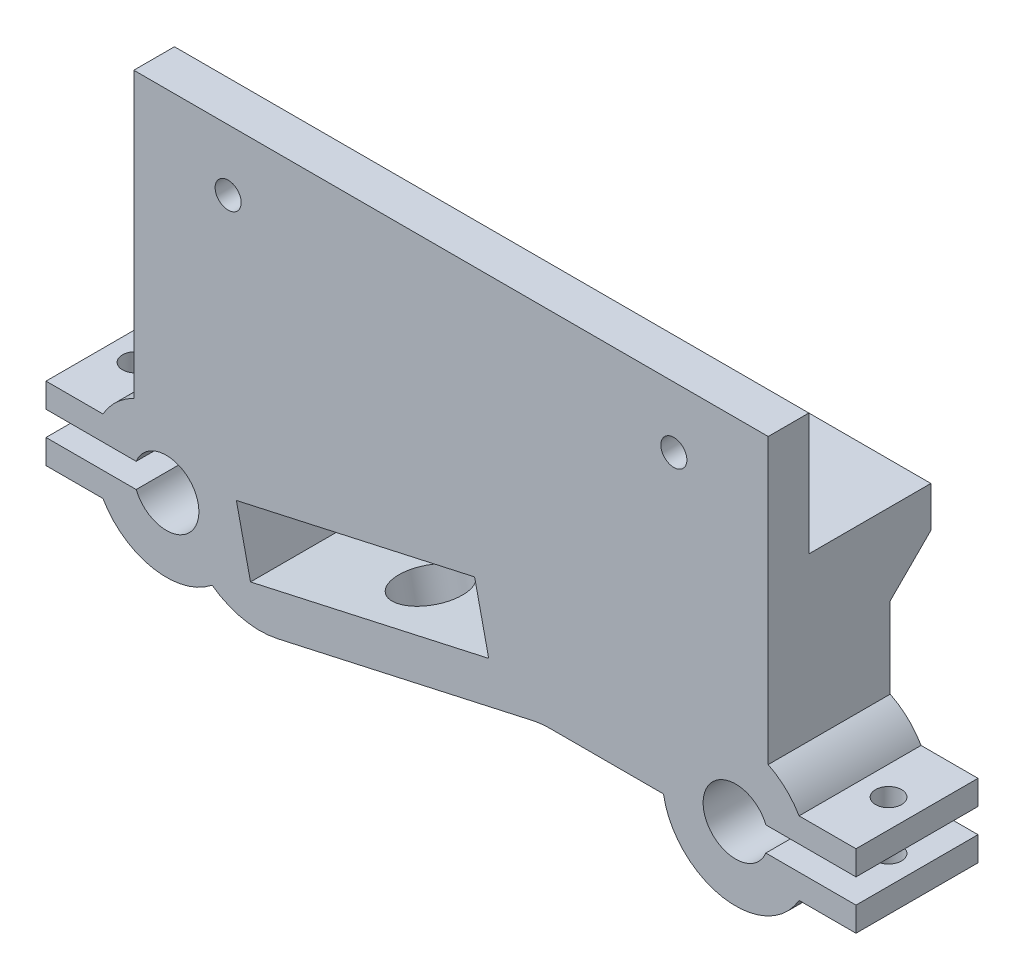
SolidWorks part; units mm, degrees
ref_plane "Front Plane" through (0, 0, 0) normal (0, 0, 1) x (1, 0, 0)
ref_plane "Top Plane" through (0, 0, 0) normal (0, 1, 0) x (1, 0, 0)
ref_plane "Right Plane" through (0, 0, 0) normal (1, 0, 0) x (0, 0, -1)
sketch "Sketch1" plane through (0, 0, 0) normal (0, 0, 1) x (1, 0, 0)
  line L0 (0, -1000) -> (0, 49000) construction
  line L1 (-39, 28) -> (39, 28)
  line L2 (39, 28) -> (39, 8.0623)
  line L3 (36.951, -8.786) -> (-23.8235, -22.2816)
  line L4 (-39, 28) -> (-39, 8.0623)
  line L6 (-34, 23) -> (34, 23)
  line L7 (34, 23) -> (34, 8.9443)
  line L9 (-13.0714, 45.025) -> (10825.8602, -48765.5982) construction
  line L10 (-1035, 0) -> (48965, 0) construction
  line L11 (-34, 23) -> (-34, 8.9443)
  line L12 (-22.3817, -16.8397) -> (-31.7139, -8.3786)
  line L13 (-23.8235, -22.2816) -> (-41.0451, -6.6675)
  line L14 (27.9966, -5.6526) -> (-22.3817, -16.8397)
  line L15 (-49.7942, 4.5) -> (-42.7942, 4.5)
  line L16 (-49.7942, 4.5) -> (-49.7942, 1.5)
  line L17 (-49.7942, 1.5) -> (-38.7081, 1.5)
  line L18 (42.7942, 4.5) -> (49.7942, 4.5)
  line L19 (-49.7942, -1.5) -> (-38.7081, -1.5)
  line L20 (-49.7942, -1.5) -> (-49.7942, -4.5)
  line L21 (-49.7942, -4.5) -> (-42.7942, -4.5)
  line L23 (38.7081, 1.5) -> (49.7942, 1.5)
  line L24 (49.7942, 4.5) -> (49.7942, 1.5)
  line L25 (38.7081, -1.5) -> (49.7942, -1.5)
  line L27 (42.7942, -4.5) -> (49.7942, -4.5)
  line L28 (49.7942, -1.5) -> (49.7942, -4.5)
  arc A0 (-38.7081, -1.5) -> (-38.7081, 1.5) centre (-35, 0) ccw
  arc A1 (38.7081, 1.5) -> (38.7081, -1.5) centre (35, 0) ccw
  arc A2 (34, 8.9443) -> (27.9966, -5.6526) centre (35, 0) ccw
  arc A3 (-39, 8.0623) -> (-42.7942, 4.5) centre (-35, 0) ccw
  arc A4 (-42.7942, -4.5) -> (-41.0451, -6.6675) centre (-35, 0) ccw
  arc A5 (-31.7139, -8.3786) -> (-34, 8.9443) centre (-35, 0) ccw
  arc A6 (36.951, -8.786) -> (42.7942, -4.5) centre (35, 0) ccw
  arc A8 (42.7942, 4.5) -> (39, 8.0623) centre (35, 0) ccw
  dimension "D1" = 8
  dimension "D2" = 70
  dimension "D4" = 18
  dimension "D5" = 19
  dimension "D14" = 9
  dimension "D3" = 102.52
  dimension "D6" = 5
  dimension "D7" = 5
  dimension "D8" = 3
  dimension "D9" = 3
  dimension "D10" = 22.5
  dimension "D11" = 5
  dimension "D12" = 5
  dimension "D13" = 3
  dimension "D15" = 7
  dimension "D16" = 3
  dimension "D17" = 7
  dimension "D18" = 5
  dimension "D19" = 90
  dimension "D20" = 3
sketch "Sketch2" plane through (0, 0, 0) normal (0, 0, 1) x (1, 0, 0)
  line L0 (-39, 28) -> (39, 28)
  line L1 (39, 28) -> (39, 8.0623)
  line L2 (-39, 28) -> (-39, 8.0623)
  line L3 (-42.7942, 4.5) -> (-49.7942, 4.5)
  line L4 (-49.7942, 4.5) -> (-49.7942, 1.5)
  line L5 (-49.7942, 1.5) -> (-38.7081, 1.5)
  line L6 (-38.7081, -1.5) -> (-49.7942, -1.5)
  line L7 (-49.7942, -1.5) -> (-49.7942, -4.5)
  line L8 (-49.7942, -4.5) -> (-42.7942, -4.5)
  line L9 (11.0821, -1.5) -> (-25.8131, -9.693)
  line L10 (42.7942, 4.5) -> (49.7942, 4.5)
  line L11 (49.7942, 4.5) -> (49.7942, 1.5)
  line L12 (49.7942, 1.5) -> (38.7081, 1.5)
  line L13 (38.7081, -1.5) -> (49.7942, -1.5)
  line L14 (49.7942, -1.5) -> (49.7942, -4.5)
  line L15 (49.7942, -4.5) -> (42.7942, -4.5)
  line L16 (-25.8131, -9.693) -> (-29.3708, -7.0223)
  line L17 (26.1259, -1.5) -> (11.0821, -1.5)
  line L19 (27.9966, -5.6526) -> (-22.3817, -16.8397) construction
  line L20 (-43369.1498, 195289.1042) -> (54181.9386, -244009.6774) construction
  line L21 (-23.3484, 3.6588) -> (0.0809, 8.8615) construction
  line L22 (-23.3484, 3.6588) -> (-21.8309, -3.1747) construction
  line L23 (-21.8309, -3.1747) -> (1.5984, 2.028) construction
  line L24 (0.0809, 8.8615) -> (1.5984, 2.028) construction
  line L25 (-16.9288, 30.1055) -> (10822.0908, -48780.9143) construction
  line L27 (-24.6512, -4.3132) -> (-26.3854, 3.4966)
  line L28 (-26.3854, 3.4966) -> (2.9012, 10)
  line L29 (2.9012, 10) -> (4.6354, 2.1902)
  line L30 (4.6354, 2.1902) -> (-24.6512, -4.3132)
  line L32 (2.9012, 10) -> (-1.0959, 28) construction
  arc A0 (-39, 8.0623) -> (-42.7942, 4.5) centre (-35, 0) ccw
  arc A1 (-39, 8.0623) -> (-42.7942, 4.5) centre (-35, 0) ccw construction
  arc A2 (39, 8.0623) -> (42.7942, 4.5) centre (35, 0) cw
  arc A3 (42.7942, 4.5) -> (39, 8.0623) centre (35, 0) ccw construction
  arc A4 (42.7942, -4.5) -> (26.1259, -1.5) centre (35, 0) cw
  arc A5 (-42.7942, -4.5) -> (-29.3708, -7.0223) centre (-35, 0) ccw
  arc A6 (-38.7081, 1.5) -> (-38.7081, -1.5) centre (-35, 0) cw
  arc A7 (-38.7081, -1.5) -> (-38.7081, 1.5) centre (-35, 0) ccw construction
  arc A8 (38.7081, 1.5) -> (38.7081, -1.5) centre (35, 0) ccw
  arc A9 (38.7081, 1.5) -> (38.7081, -1.5) centre (35, 0) ccw construction
  dimension "D1" = 24
  dimension "D2" = 5
  dimension "D3" = 7
  dimension "D4" = 30
  dimension "D5" = 8
  dimension "D6" = 0.5
  dimension "D7" = 18
  dimension "D8" = 5
  dimension "D9" = 5
extrude "Boss-Extrude1" add sketch "Sketch2" against normal blind 15
sketch "Sketch3" plane through (0, 0, -15) normal (0, 0, -1) x (-1, 0, 0)
  line L0 (-34, 8.9443) -> (-34, 23)
  line L1 (-34, 23) -> (34, 23)
  line L2 (34, 23) -> (34, 8.9443)
  line L3 (-30.9373, 8.0309) -> (24.6512, -4.3132)
  line L4 (24.6512, -4.3132) -> (-4.6354, 2.1902) construction
  line L5 (24.6512, -4.3132) -> (26.3854, 3.4966)
  line L6 (26.3854, 3.4966) -> (27.0373, 4.1946)
  arc A0 (-27.9966, -5.6526) -> (-34, 8.9443) centre (-35, 0) ccw construction
  arc A2 (34, 8.9443) -> (27.0373, 4.1946) centre (35, 0) ccw
  arc A3 (-34, 8.9443) -> (-30.9373, 8.0309) centre (-35, 0) cw
extrude "Cut-Extrude1" cut sketch "Sketch3" against normal blind 13
sketch "Sketch4" plane through (0, 0, -2) normal (0, 0, -1) x (-1, 0, 0)
  line L0 (5.8848, 8.049) -> (7.619, 15.8587)
  line L1 (26.3854, 3.4966) -> (-2.9012, 10) construction
  line L2 (19.3337, 13.2574) -> (17.5994, 5.4476)
  line L3 (7.619, 15.8587) -> (19.3337, 13.2574)
  line L4 (5.8848, 8.049) -> (17.5994, 5.4476)
  line L5 (9.8325, -1.8514) -> (10848.8521, 48809.1684) construction
  line L6 (43369.1498, 195289.1042) -> (-54181.9386, -244009.6774) construction
  line L7 (-2.9012, 10) -> (-4.6354, 2.1902) construction
  line L8 (26.3854, 3.4966) -> (24.6512, -4.3132) construction
  dimension "D1" = 12
  dimension "D2" = 8
extrude "Boss-Extrude2" add sketch "Sketch4" along normal blind 13
sketch "Sketch5" plane through (0.8382, -3.7748, 0) normal (0.2168, -0.9762, 0) x (0.9762, 0.2168, 0)
  line L0 (-1010.1244, -7.5) -> (48989.8756, -7.5) construction
  line L2 (-10, -1013.6456) -> (-10, 48986.3544) construction
  line L9 (-4, -15) -> (-4, -2) construction
  line L10 (-16, -15) -> (-16, -2) construction
  line L11 (-27.3006, -15) -> (10.4934, -15) construction
  line L12 (-27.3006, 0) -> (10.4934, 0) construction
  circle A0 centre (-10, -7.5) radius 4
  dimension "D1" = 8
extrude "Cut-Extrude2" cut sketch "Sketch5" against normal offset from surface (18 mm away) 5 up to face at (-11.7421, 6.7483, -4.75) offset beyond the face yes
sketch "Sketch6" plane through (0, 28, 0) normal (0, 1, 0) x (1, 0, 0)
  line L0 (39, 15) -> (39, 0) construction
  line L1 (-39, 0) -> (39, 0)
  line L2 (-39, 0) -> (-39, 5)
  line L3 (-39, 5) -> (39, 5)
  line L4 (39, 0) -> (39, 5)
  dimension "D1" = 5
extrude "Boss-Extrude3" add sketch "Sketch6" along normal blind 15
sketch "Sketch7" plane through (0, 0, -15) normal (0, 0, -1) x (-1, 0, 0)
  line L0 (-39, 8.0623) -> (-39, 28) construction
  line L1 (39, 28) -> (-39, 28)
  line L2 (39, 28) -> (39, 23)
  line L3 (39, 23) -> (-39, 23)
  line L4 (-39, 28) -> (-39, 23)
  line L5 (34, 23) -> (-34, 23) construction
extrude "Boss-Extrude4" add sketch "Sketch7" along normal blind 5
sketch "Sketch8" plane through (0, 0, -5) normal (0, 0, -1) x (-1, 0, 0)
  line L0 (-961, 35.5) -> (49039, 35.5) construction
  line L1 (39, 43) -> (39, 28) construction
  line L2 (-39, 43) -> (-39, 28) construction
  circle A0 centre (27.4, 35.5) radius 1.6
  circle A1 centre (-27.4, 35.5) radius 1.6
  point P9 (39, 35.5)
  dimension "D1" = 3.2
  dimension "D2" = 11.6
  dimension "D3" = 11.6
extrude "Cut-Extrude3" cut sketch "Sketch8" against normal up to next
sketch "Sketch9" plane through (0, 28, 0) normal (0, 1, 0) x (1, 0, 0)
  line L0 (-1039, 12.5) -> (48961, 12.5) construction
  line L1 (-39, 20) -> (-39, 5) construction
  line L4 (39, 20) -> (39, 5) construction
  circle A0 centre (-27.4, 12.5) radius 1.6
  circle A1 centre (27.4, 12.5) radius 1.6
  point P5 (-39, 12.5)
  dimension "D1" = 3.2
  dimension "D2" = 11.6
  dimension "D3" = 11.6
extrude "Cut-Extrude4" cut sketch "Sketch9" against normal up to next
chamfer "Chamfer1" distance 5 angle 45 2 edges at (36.5, 23, -15) (-36.5, 23, -15)
fillet "Fillet1" radius 3 3 edges at (-13.4764, 14.5581, -15) (-18.4666, 9.3525, -15) (-6.7519, 11.9539, -15)
sketch "Sketch10" plane through (0, -4.5, 0) normal (0, -1, 0) x (1, 0, 0)
  line L0 (46.2942, -1015) -> (46.2942, 48985) construction
  line L1 (42.7942, -15) -> (49.7942, -15) construction
  line L2 (-46.2942, -1015) -> (-46.2942, 48985) construction
  line L3 (-49.7942, -15) -> (-42.7942, -15) construction
  line L4 (-950.2058, -7.5) -> (49049.7942, -7.5) construction
  line L5 (49.7942, -15) -> (49.7942, 0) construction
  circle A0 centre (46.2942, -7.5) radius 1.6
  circle A1 centre (-46.2942, -7.5) radius 1.6
  point P9 (46.2942, -15)
  point P14 (-46.2942, -15)
  point P19 (49.7942, -7.5)
  dimension "D1" = 3.2
extrude "Cut-Extrude5" cut sketch "Sketch10" against normal through all
fillet "Fillet2" radius 10 2 edges at (11.0821, -1.5, -7.5) (-25.8131, -9.693, -7.5)
